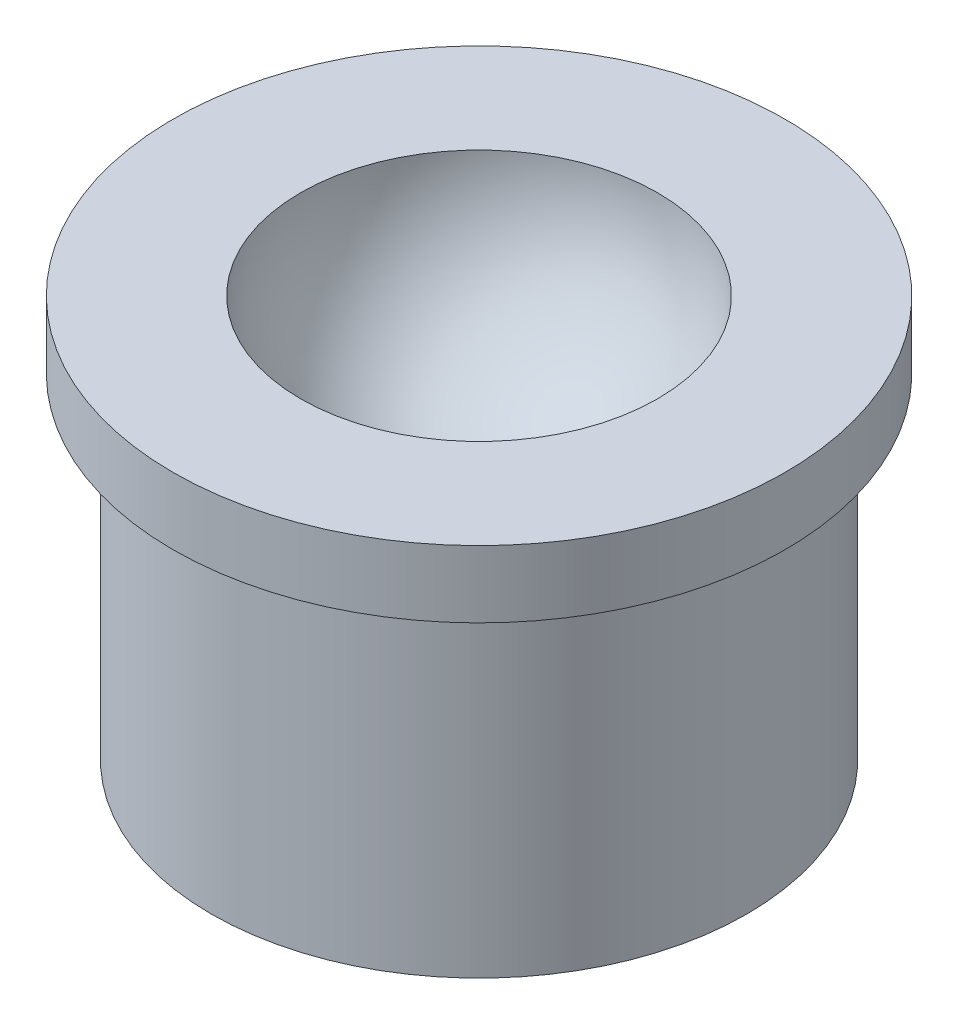
SolidWorks part; units mm, degrees
ref_plane "Front Plane" through (0, 0, 0) normal (0, 0, 1) x (1, 0, 0)
ref_plane "Top Plane" through (0, 0, 0) normal (0, 1, 0) x (1, 0, 0)
ref_plane "Right Plane" through (0, 0, 0) normal (1, 0, 0) x (0, 0, -1)
sketch "Sketch1" plane through (0, 0, 0) normal (0, 0, 1) x (1, 0, 0)
  line L0 (0, 15.6222) -> (0, -14.9021) construction
  line L1 (0, 0) -> (6.35, 0)
  line L2 (6.35, 0) -> (6.35, 7.9375)
  line L3 (6.35, 7.9375) -> (7.2571, 7.9375)
  line L4 (7.2571, 7.9375) -> (7.2571, 9.525)
  line L5 (7.2571, 9.525) -> (0, 9.525)
  line L6 (0, 9.525) -> (0, 0)
  dimension "D1" = 12.7
  dimension "D2" = 14.5143
  dimension "D3" = 7.9375
  dimension "D4" = 1.5875
revolve "Revolve1" add sketch "Sketch1" angle 360 about L0
sketch "Sketch2" plane through (0, 0, 0) normal (0, 0, 1) x (1, 0, 0)
  line L0 (7.2571, 9.525) -> (-7.2571, 9.525) construction
  line L1 (0, 0) -> (0, 14.3345) construction
  line L2 (4.2333, 9.525) -> (0, 9.525)
  line L3 (0, 9.525) -> (0, 5.2917)
  arc A0 (0, 5.2917) -> (4.2333, 9.525) centre (0, 9.525) ccw
  dimension "D1" = 8.4667
revolve "Cut-Revolve3" cut sketch "Sketch2" angle 360 about L1
